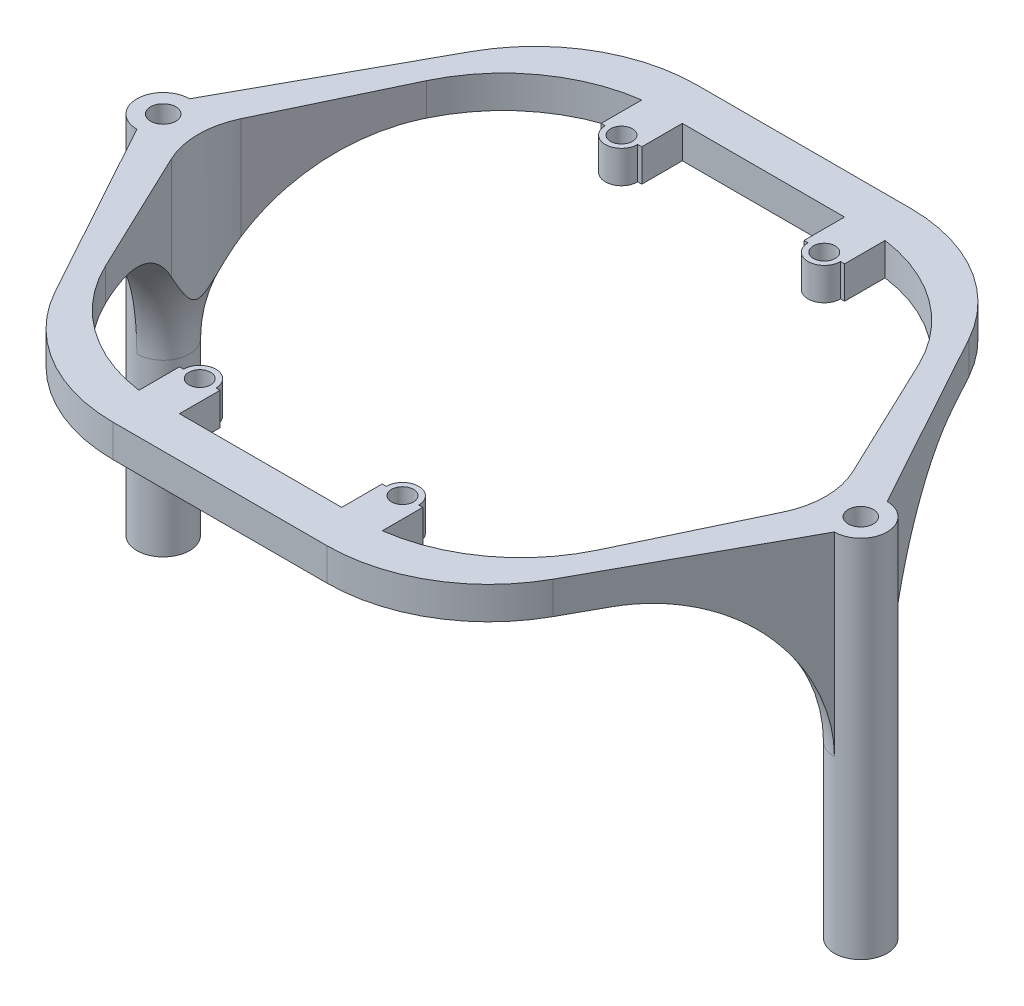
SolidWorks part; units mm, degrees
ref_plane "Front Plane" through (0, 0, 0) normal (0, 0, 1) x (1, 0, 0)
ref_plane "Top Plane" through (0, 0, 0) normal (0, 1, 0) x (1, 0, 0)
ref_plane "Right Plane" through (0, 0, 0) normal (1, 0, 0) x (0, 0, -1)
sketch "Sketch3" plane through (0, 0, 0) normal (0, 1, 0) x (1, 0, 0)
  line L0 (-43.8416, 0) -> (42.1584, 0) construction
  circle A0 centre (-43.8416, 0) radius 1.55
  circle A1 centre (42.1584, 0) radius 1.55
  circle A2 centre (-43.8416, 0) radius 3.25
  circle A3 centre (42.1584, 0) radius 3.25
extrude "Boss-Extrude2" add sketch "Sketch3" along normal blind 45
sketch "Sketch4" plane through (0, 45, 0) normal (0, 1, 0) x (1, 0, 0)
  line L2 (-0.8416, 0) -> (-0.8416, -3.25) construction
  line L3 (-0.8416, 0) -> (-0.8416, -3.25) construction
  line L4 (-15.8416, 26) -> (-15.8416, 31)
  line L5 (-11.9916, 26) -> (-13.3416, 26) construction
  line L6 (10.3084, 26) -> (11.6584, 26) construction
  line L7 (-11.9916, -26) -> (-13.3416, -26) construction
  line L8 (10.3084, -26) -> (11.6584, -26) construction
  line L9 (14.1584, 26) -> (14.1584, 31)
  line L10 (-10.8416, 31) -> (9.1584, 31)
  line L11 (-10.8416, -31) -> (9.1584, -31)
  line L12 (-15.8416, 31) -> (-25.8416, 31)
  line L35 (-0.8416, 23.5) -> (-0.8416, 26) construction
  line L36 (-0.8416, -23.5) -> (-0.8416, -26) construction
  line L37 (-15.8416, -26) -> (-15.8416, -31)
  line L38 (14.1584, -26) -> (14.1584, -31)
  line L39 (-10.8416, -26) -> (-10.8416, -31)
  line L40 (9.1584, -26) -> (9.1584, -31)
  line L41 (-10.8416, 26) -> (-10.8416, 31)
  line L42 (9.1584, 26) -> (9.1584, 31)
  line L43 (14.1584, 31) -> (24.1584, 31)
  line L44 (-15.8416, -31) -> (-25.8416, -31)
  line L45 (14.1584, -31) -> (24.1584, -31)
  line L46 (-25.8416, 31) -> (-40.5916, 0)
  line L47 (-25.8416, -31) -> (-40.5916, 0)
  line L48 (24.1584, 31) -> (38.9084, 0)
  line L49 (24.1584, -31) -> (38.9084, 0)
  line L50 (-15.8416, 26) -> (-15.3416, 26)
  line L51 (-11.3416, 26) -> (-10.8416, 26)
  line L52 (9.1584, 26) -> (9.6584, 26)
  line L53 (13.6584, 26) -> (14.1584, 26)
  line L54 (9.1584, -26) -> (9.6584, -26)
  line L55 (-25.8416, 36) -> (-43.8416, 3.25)
  line L56 (-43.8416, -3.25) -> (-25.8416, -36)
  line L57 (24.1584, 36) -> (42.1584, 3.25)
  line L58 (42.1584, -3.25) -> (24.1584, -36)
  line L59 (-25.8416, -36) -> (24.1584, -36)
  line L60 (-25.8416, 36) -> (24.1584, 36)
  line L61 (14.1584, -26) -> (13.6584, -26)
  line L62 (-15.8416, -26) -> (-15.3416, -26)
  line L63 (-10.8416, -26) -> (-11.3416, -26)
  circle A2 centre (-13.3416, 26) radius 1.35
  circle A3 centre (11.6584, 26) radius 1.35
  circle A4 centre (-13.3416, -26) radius 1.35
  circle A5 centre (11.6584, -26) radius 1.35
  arc A16 (-43.8416, -3.25) -> (-43.8416, 3.25) centre (-43.8416, 0) ccw
  arc A17 (42.1584, 3.25) -> (42.1584, -3.25) centre (42.1584, 0) ccw
  arc A18 (-11.3416, -26) -> (-15.3416, -26) centre (-13.3416, -26) ccw
  arc A19 (13.6584, -26) -> (9.6584, -26) centre (11.6584, -26) ccw
  arc A20 (-15.3416, 26) -> (-11.3416, 26) centre (-13.3416, 26) ccw
  arc A21 (9.6584, 26) -> (13.6584, 26) centre (11.6584, 26) ccw
extrude "Boss-Extrude3" add sketch "Sketch4" against normal blind 4
fillet "Fillet1" radius 20 12 edges at (39.8603, 41, -2.2981) (24.1584, 43, -36) (-25.8416, 43, -36) (-25.8416, 43, 36) (24.1584, 43, 36) (39.8603, 41, 2.2981) (-41.5435, 41, 2.2981) (-41.5435, 41, -2.2981) (-25.8416, 43, 31) (24.1584, 43, 31) (-25.8416, 43, -31) (24.1584, 43, -31)
fillet "Fillet2" radius 10 2 edges at (38.9084, 33, 0) (-40.5916, 33, 0)
